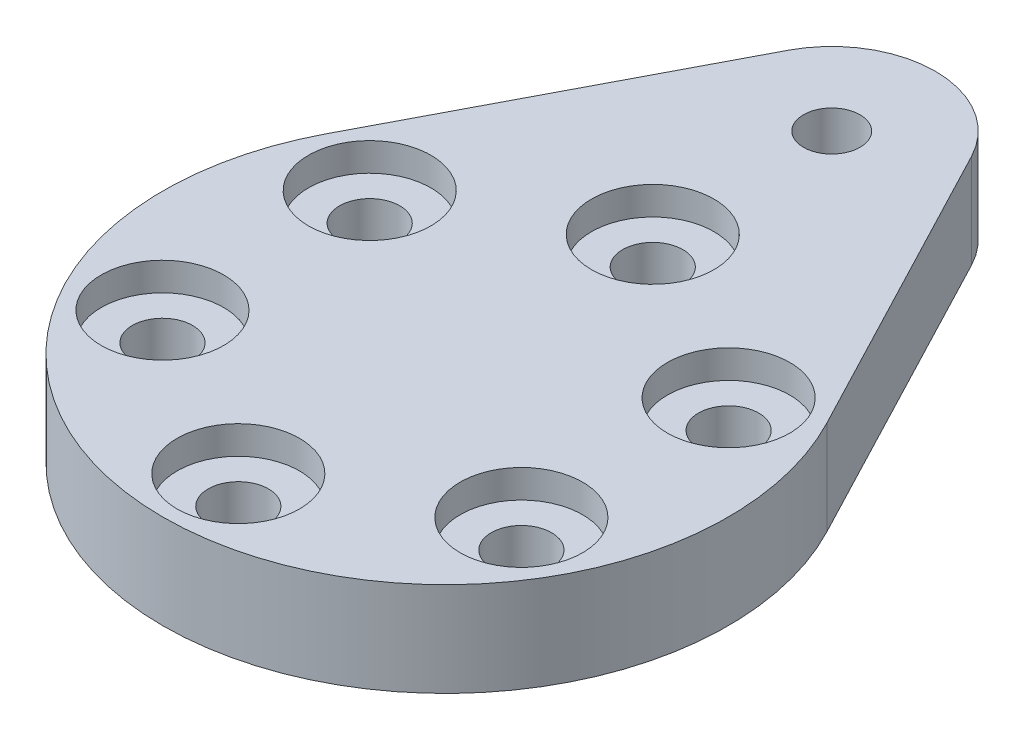
SolidWorks part; units mm, degrees
ref_plane "Front Plane" through (0, 0, 0) normal (0, 0, 1) x (1, 0, 0)
ref_plane "Top Plane" through (0, 0, 0) normal (0, 1, 0) x (1, 0, 0)
ref_plane "Right Plane" through (0, 0, 0) normal (1, 0, 0) x (0, 0, -1)
sketch "Sketch4" plane through (0, 0, 0) normal (0, 1, 0) x (1, 0, 0)
  line L0 (0, 0) -> (0, 20.5) construction
  line L1 (-4.8738, 23.0488) -> (-13.2921, 6.9512)
  line L2 (4.8738, 23.0488) -> (13.2921, 6.9512)
  circle A0 centre (0, 0) radius 11 construction
  circle A1 centre (0, 0) radius 15
  circle A2 centre (0, 11) radius 1.6
  circle A3 centre (9.5263, 5.5) radius 1.6
  circle A4 centre (9.5263, -5.5) radius 1.6
  circle A5 centre (0, -11) radius 1.6
  circle A6 centre (-9.5263, -5.5) radius 1.6
  circle A7 centre (-9.5263, 5.5) radius 1.6
  circle A8 centre (0, 20.5) radius 1.5
  circle A9 centre (0, 20.5) radius 5.5
  point P18 (0, 0)
  dimension "D1" = 22
  dimension "D2" = 30
  dimension "D3" = 3.2
  dimension "D6" = 3
  dimension "D5" = 20.5
  dimension "D4" = 6
extrude "Boss-Extrude1" add sketch "Sketch4" along normal blind 5 contours A9 A8 | A9 L1 A1 | A9 A1 L2 | A1 A7 A6 A5 A4 A3 A2 region at (-6.7798, 0, -15.4196) region at (0, 0, -25.8444) region at (0, 0, 0) region at (6.7798, 0, -15.4196)
sketch "Sketch6" plane through (0, 5, 0) normal (0, 1, 0) x (1, 0, 0)
  circle A0 centre (0, 0) radius 11 construction
  circle A1 centre (0, 11) radius 3.25
  circle A2 centre (9.5263, 5.5) radius 3.25
  circle A3 centre (9.5263, -5.5) radius 3.25
  circle A4 centre (0, -11) radius 3.25
  circle A5 centre (-9.5263, -5.5) radius 3.25
  circle A6 centre (-9.5263, 5.5) radius 3.25
  point P19 (0, 0)
  dimension "D1" = 6.5
  dimension "D3" = 22
  dimension "D2" = 6
extrude "Cut-Extrude1" cut sketch "Sketch6" against normal blind 1.5
